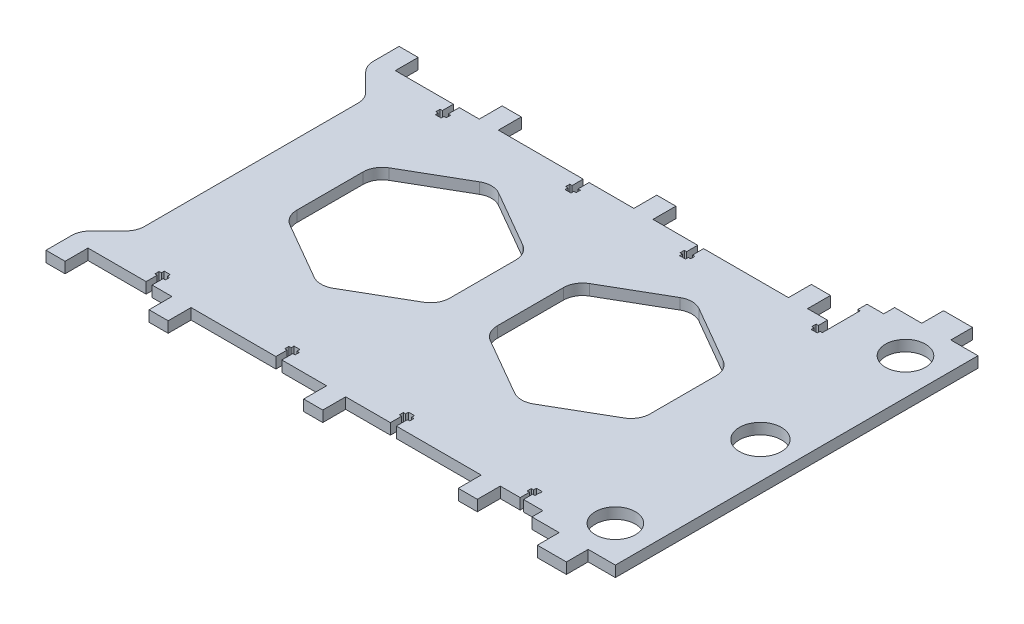
SolidWorks part; units mm, degrees
ref_plane "Спереди" through (0, 0, 0) normal (0, 0, 1) x (1, 0, 0)
ref_plane "Сверху" through (0, 0, 0) normal (0, 1, 0) x (1, 0, 0)
ref_plane "Справа" through (0, 0, 0) normal (1, 0, 0) x (0, 0, -1)
sketch "Эскиз1" plane through (0, 0, 0) normal (0, 1, 0) x (1, 0, 0)
  line L32 (-23.9169, 26.9382) -> (-55.4959, 45.1703)
  line L33 (-66.0222, 45.1703) -> (-97.6012, 26.9382)
  line L34 (-102.8643, 17.8222) -> (-102.8643, -18.6421)
  line L35 (-97.6012, -27.7581) -> (-66.0222, -45.9902)
  line L36 (-55.4959, -45.9902) -> (-23.9169, -27.7581)
  line L37 (-18.6538, -18.6421) -> (-18.6538, 17.8222)
  line L38 (12.9252, -27.7581) -> (44.5041, -45.9902)
  line L39 (55.0304, -45.9902) -> (86.6094, -27.7581)
  line L40 (91.8726, -18.6421) -> (91.8726, 17.8222)
  line L41 (86.6094, 26.9382) -> (55.0304, 45.1703)
  line L42 (44.5041, 45.1703) -> (12.9252, 26.9382)
  line L43 (7.662, 17.8222) -> (7.662, -18.6421)
  line L44 (-137.0749, -68.4709) -> (-137.0749, 49.1247)
  line L45 (-140.158, 56.5679) -> (-149.7813, 66.1912)
  line L46 (-152.8644, 87.6954) -> (-152.8644, 73.6344)
  line L47 (-152.8644, 87.6954) -> (-142.338, 87.6954)
  line L48 (-142.338, 87.6954) -> (-142.338, 75.0638)
  line L49 (-142.338, 75.0638) -> (-110.2854, 75.0638)
  line L50 (-110.2854, 75.0638) -> (-110.2854, 68.9585)
  line L51 (-110.2854, 68.9585) -> (-111.5486, 68.9585)
  line L52 (-111.5486, 68.9585) -> (-111.5486, 66.6427)
  line L53 (-111.5486, 66.6427) -> (-110.2854, 66.6427)
  line L54 (-110.2854, 66.6427) -> (-110.2854, 65.0638)
  line L55 (-110.2854, 65.0638) -> (-107.0222, 65.0638)
  line L56 (-107.0222, 65.0638) -> (-107.0222, 66.6427)
  line L57 (-107.0222, 66.6427) -> (-105.7591, 66.6427)
  line L58 (-105.7591, 66.6427) -> (-105.7591, 68.9585)
  line L59 (-105.7591, 68.9585) -> (-107.0222, 68.9585)
  line L60 (-107.0222, 68.9585) -> (-107.0222, 75.0638)
  line L61 (-107.0222, 75.0638) -> (-96.0222, 75.0638)
  line L62 (-96.0222, 75.0638) -> (-96.0222, 87.6954)
  line L63 (-96.0222, 87.6954) -> (-85.4959, 87.6954)
  line L64 (-85.4959, 87.6954) -> (-85.4959, 75.0638)
  line L65 (-85.4959, 75.0638) -> (-38.7064, 75.0638)
  line L66 (-38.7064, 75.0638) -> (-38.7064, 68.9585)
  line L67 (-38.7064, 68.9585) -> (-39.9696, 68.9585)
  line L68 (-39.9696, 68.9585) -> (-39.9696, 66.6427)
  line L69 (-39.9696, 66.6427) -> (-38.7064, 66.6427)
  line L70 (-38.7064, 66.6427) -> (-38.7064, 65.0638)
  line L71 (-38.7064, 65.0638) -> (-35.4433, 65.0638)
  line L72 (-35.4433, 65.0638) -> (-35.4433, 66.6427)
  line L73 (-35.4433, 66.6427) -> (-34.1801, 66.6427)
  line L74 (-34.1801, 66.6427) -> (-34.1801, 68.9585)
  line L75 (-34.1801, 68.9585) -> (-35.4433, 68.9585)
  line L76 (-35.4433, 68.9585) -> (-35.4433, 75.0638)
  line L77 (-35.4433, 75.0638) -> (-10.7591, 75.0638)
  line L78 (-10.7591, 75.0638) -> (-10.7591, 87.6954)
  line L79 (-10.7591, 87.6954) -> (-0.2327, 87.6954)
  line L80 (-0.2327, 87.6954) -> (-0.2327, 75.0638)
  line L81 (-0.2327, 75.0638) -> (24.4515, 75.0638)
  line L82 (24.4515, 75.0638) -> (24.4515, 68.9585)
  line L83 (24.4515, 68.9585) -> (23.1883, 68.9585)
  line L84 (23.1883, 68.9585) -> (23.1883, 66.6427)
  line L85 (23.1883, 66.6427) -> (24.4515, 66.6427)
  line L86 (24.4515, 66.6427) -> (24.4515, 65.0638)
  line L87 (24.4515, 65.0638) -> (27.7146, 65.0638)
  line L88 (27.7146, 65.0638) -> (27.7146, 66.6427)
  line L89 (27.7146, 66.6427) -> (28.9778, 66.6427)
  line L90 (28.9778, 66.6427) -> (28.9778, 68.9585)
  line L91 (28.9778, 68.9585) -> (27.7146, 68.9585)
  line L92 (27.7146, 68.9585) -> (27.7146, 75.0638)
  line L93 (27.7146, 75.0638) -> (74.5041, 75.0638)
  line L94 (74.5041, 75.0638) -> (74.5041, 87.6954)
  line L95 (74.5041, 87.6954) -> (85.0304, 87.6954)
  line L96 (85.0304, 87.6954) -> (85.0304, 75.0638)
  line L97 (85.0304, 75.0638) -> (96.0304, 75.0638)
  line L98 (96.0304, 75.0638) -> (96.0304, 70.0111)
  line L99 (96.0304, 70.0111) -> (94.7673, 70.0111)
  line L100 (94.7673, 70.0111) -> (94.7673, 67.6954)
  line L101 (94.7673, 67.6954) -> (96.0304, 67.6954)
  line L102 (96.0304, 67.6954) -> (96.0304, 66.1164)
  line L103 (96.0304, 66.1164) -> (99.2936, 66.1164)
  line L104 (99.2936, 66.1164) -> (99.2936, 67.6954)
  line L105 (99.2936, 67.6954) -> (100.5568, 67.6954)
  line L106 (100.5568, 67.6954) -> (100.5568, 88.5374)
  line L107 (100.5568, 88.5374) -> (99.2936, 88.5374)
  line L108 (99.2936, 88.5374) -> (99.2936, 93.5901)
  line L109 (99.2936, 93.5901) -> (108.5041, 93.5901)
  line L110 (108.5041, 93.5901) -> (108.5041, 99.5901)
  line L111 (108.5041, 99.5901) -> (123.5041, 99.5901)
  line L112 (123.5041, 99.5901) -> (123.5041, 111.5901)
  line L113 (123.5041, 111.5901) -> (139.5041, 111.5901)
  line L114 (139.5041, 111.5901) -> (139.5041, 99.5901)
  line L115 (139.5041, 99.5901) -> (154.5041, 99.5901)
  line L116 (154.5041, -100.4099) -> (154.5041, 99.5901)
  line L117 (139.5041, -100.4099) -> (154.5041, -100.4099)
  line L118 (139.5041, -112.4099) -> (139.5041, -100.4099)
  line L119 (123.5041, -112.4099) -> (139.5041, -112.4099)
  line L120 (123.5041, -100.4099) -> (123.5041, -112.4099)
  line L121 (108.5041, -100.4099) -> (123.5041, -100.4099)
  line L122 (108.5041, -94.4099) -> (108.5041, -100.4099)
  line L123 (97.8462, -94.4099) -> (108.5041, -94.4099)
  line L124 (97.8462, -89.3573) -> (97.8462, -94.4099)
  line L125 (99.1094, -89.3573) -> (97.8462, -89.3573)
  line L126 (99.1094, -87.0415) -> (99.1094, -89.3573)
  line L127 (99.2936, -87.0415) -> (99.1094, -87.0415)
  line L128 (99.2936, -85.4626) -> (99.2936, -87.0415)
  line L129 (96.0305, -85.4626) -> (99.2936, -85.4626)
  line L130 (96.0305, -87.0415) -> (96.0305, -85.4626)
  line L131 (94.7673, -87.0415) -> (96.0305, -87.0415)
  line L132 (94.7673, -89.3573) -> (94.7673, -87.0415)
  line L133 (96.0305, -89.3573) -> (94.7673, -89.3573)
  line L134 (96.0305, -94.4099) -> (96.0305, -89.3573)
  line L135 (85.0305, -94.4099) -> (96.0305, -94.4099)
  line L136 (85.0305, -107.0415) -> (85.0305, -94.4099)
  line L137 (74.5041, -107.0415) -> (85.0305, -107.0415)
  line L138 (74.5041, -94.4099) -> (74.5041, -107.0415)
  line L139 (27.7146, -94.4099) -> (74.5041, -94.4099)
  line L140 (27.7146, -88.3047) -> (27.7146, -94.4099)
  line L141 (28.9778, -88.3047) -> (27.7146, -88.3047)
  line L142 (28.9778, -85.9889) -> (28.9778, -88.3047)
  line L143 (27.7146, -85.9889) -> (28.9778, -85.9889)
  line L144 (27.7146, -84.4099) -> (27.7146, -85.9889)
  line L145 (24.4515, -84.4099) -> (27.7146, -84.4099)
  line L146 (24.4515, -85.9889) -> (24.4515, -84.4099)
  line L147 (23.1883, -85.9889) -> (24.4515, -85.9889)
  line L148 (23.1883, -88.3047) -> (23.1883, -85.9889)
  line L149 (24.4515, -88.3047) -> (23.1883, -88.3047)
  line L150 (24.4515, -94.4099) -> (24.4515, -88.3047)
  line L151 (-0.2327, -94.4099) -> (24.4515, -94.4099)
  line L152 (-0.2327, -107.0415) -> (-0.2327, -94.4099)
  line L153 (-10.759, -107.0415) -> (-0.2327, -107.0415)
  line L154 (-10.759, -94.4099) -> (-10.759, -107.0415)
  line L155 (-35.4433, -94.4099) -> (-10.759, -94.4099)
  line L156 (-35.4433, -88.3047) -> (-35.4433, -94.4099)
  line L157 (-34.1801, -88.3047) -> (-35.4433, -88.3047)
  line L158 (-34.1801, -85.9889) -> (-34.1801, -88.3047)
  line L159 (-35.4433, -85.9889) -> (-34.1801, -85.9889)
  line L160 (-35.4433, -84.4099) -> (-35.4433, -85.9889)
  line L161 (-38.7064, -84.4099) -> (-35.4433, -84.4099)
  line L162 (-38.7064, -85.9889) -> (-38.7064, -84.4099)
  line L163 (-39.9696, -85.9889) -> (-38.7064, -85.9889)
  line L164 (-39.9696, -88.3047) -> (-39.9696, -85.9889)
  line L165 (-38.7064, -88.3047) -> (-39.9696, -88.3047)
  line L166 (-38.7064, -94.4099) -> (-38.7064, -88.3047)
  line L167 (-85.4959, -94.4099) -> (-38.7064, -94.4099)
  line L168 (-85.4959, -107.0415) -> (-85.4959, -94.4099)
  line L169 (-96.0222, -107.0415) -> (-85.4959, -107.0415)
  line L170 (-96.0222, -94.4099) -> (-96.0222, -107.0415)
  line L171 (-107.0222, -94.4099) -> (-96.0222, -94.4099)
  line L172 (-107.0222, -88.3047) -> (-107.0222, -94.4099)
  line L173 (-105.7591, -88.3047) -> (-107.0222, -88.3047)
  line L174 (-105.7591, -85.9889) -> (-105.7591, -88.3047)
  line L175 (-107.0222, -85.9889) -> (-105.7591, -85.9889)
  line L176 (-107.0222, -84.4099) -> (-107.0222, -85.9889)
  line L177 (-110.2854, -84.4099) -> (-107.0222, -84.4099)
  line L178 (-110.2854, -85.9889) -> (-110.2854, -84.4099)
  line L179 (-111.5485, -85.9889) -> (-110.2854, -85.9889)
  line L180 (-111.5485, -88.3047) -> (-111.5485, -85.9889)
  line L181 (-110.2854, -88.3047) -> (-111.5485, -88.3047)
  line L182 (-110.2854, -94.4099) -> (-110.2854, -88.3047)
  line L183 (-142.338, -94.4099) -> (-110.2854, -94.4099)
  line L184 (-142.338, -107.0415) -> (-142.338, -94.4099)
  line L185 (-152.8643, -107.0415) -> (-142.338, -107.0415)
  line L186 (-149.7813, -85.5374) -> (-140.158, -75.9141)
  line L187 (-152.8643, -92.9806) -> (-152.8643, -107.0415)
  line L188 (154.5041, 128.5638) -> (154.5041, -110.5606) construction
  line L189 (175.6449, -0.4099) -> (-201.3479, -0.4099) construction
  line L190 (169.6988, 99.5901) -> (-201.3479, 99.5901) construction
  line L191 (168.2514, -100.4099) -> (-202.7953, -100.4099) construction
  line L192 (169.6988, -94.4099) -> (-201.3479, -94.4099) construction
  line L193 (169.6988, -107.0415) -> (-201.3479, -107.0415) construction
  line L194 (108.5041, -130.2674) -> (108.5041, 111.5901) construction
  circle A3 centre (134.5041, 79.5901) radius 11.0526
  circle A10 centre (134.5041, -80.4099) radius 11.0526
  circle A14 centre (134.5041, -0.4099) radius 11.579
  arc A15 (-18.6538, 17.8222) -> (-23.9169, 26.9382) centre (-29.1801, 17.8222) ccw
  arc A16 (-55.4959, 45.1703) -> (-66.0222, 45.1703) centre (-60.7591, 36.0543) ccw
  arc A17 (-97.6012, 26.9382) -> (-102.8643, 17.8222) centre (-92.338, 17.8222) ccw
  arc A18 (-102.8643, -18.6421) -> (-97.6012, -27.7581) centre (-92.338, -18.6421) ccw
  arc A19 (-66.0222, -45.9902) -> (-55.4959, -45.9902) centre (-60.7591, -36.8742) ccw
  arc A20 (-23.9169, -27.7581) -> (-18.6538, -18.6421) centre (-29.1801, -18.6421) ccw
  arc A21 (7.662, -18.6421) -> (12.9252, -27.7581) centre (18.1883, -18.6421) ccw
  arc A22 (44.5041, -45.9902) -> (55.0304, -45.9902) centre (49.7673, -36.8742) ccw
  arc A23 (86.6094, -27.7581) -> (91.8726, -18.6421) centre (81.3462, -18.6421) ccw
  arc A24 (91.8726, 17.8222) -> (86.6094, 26.9382) centre (81.3462, 17.8222) ccw
  arc A25 (55.0304, 45.1703) -> (44.5041, 45.1703) centre (49.7673, 36.0543) ccw
  arc A26 (12.9252, 26.9382) -> (7.662, 17.8222) centre (18.1883, 17.8222) ccw
  arc A27 (-140.158, -75.9141) -> (-137.0749, -68.4709) centre (-147.6012, -68.4709) ccw
  arc A28 (-137.0749, 49.1247) -> (-140.158, 56.5679) centre (-147.6012, 49.1247) ccw
  arc A29 (-152.8644, 73.6344) -> (-149.7813, 66.1912) centre (-142.338, 73.6344) ccw
  arc A30 (-149.7813, -85.5374) -> (-152.8643, -92.9806) centre (-142.338, -92.9806) ccw
  point P0 (147.0041, -100.4099)
  point P3 (154.5041, -0.4099)
  dimension "D1" = 20
  dimension "D4" = 80
  dimension "D5" = 80
  dimension "D2" = 20
  dimension "D3" = 20
  dimension "D6" = 100
  dimension "D7" = 100
  dimension "D8" = 112
  dimension "D9" = 112
  dimension "D10" = 6
  dimension "D11" = 6
  dimension "D12" = 12
  dimension "D13" = 26
  dimension "D14" = 15
  dimension "D15" = 15
  dimension "D16" = 15
  dimension "D17" = 15
  dimension "D18" = 16
  dimension "D19" = 12
extrude "Бобышка-Вытянуть1" add sketch "Эскиз1" along normal blind 6
